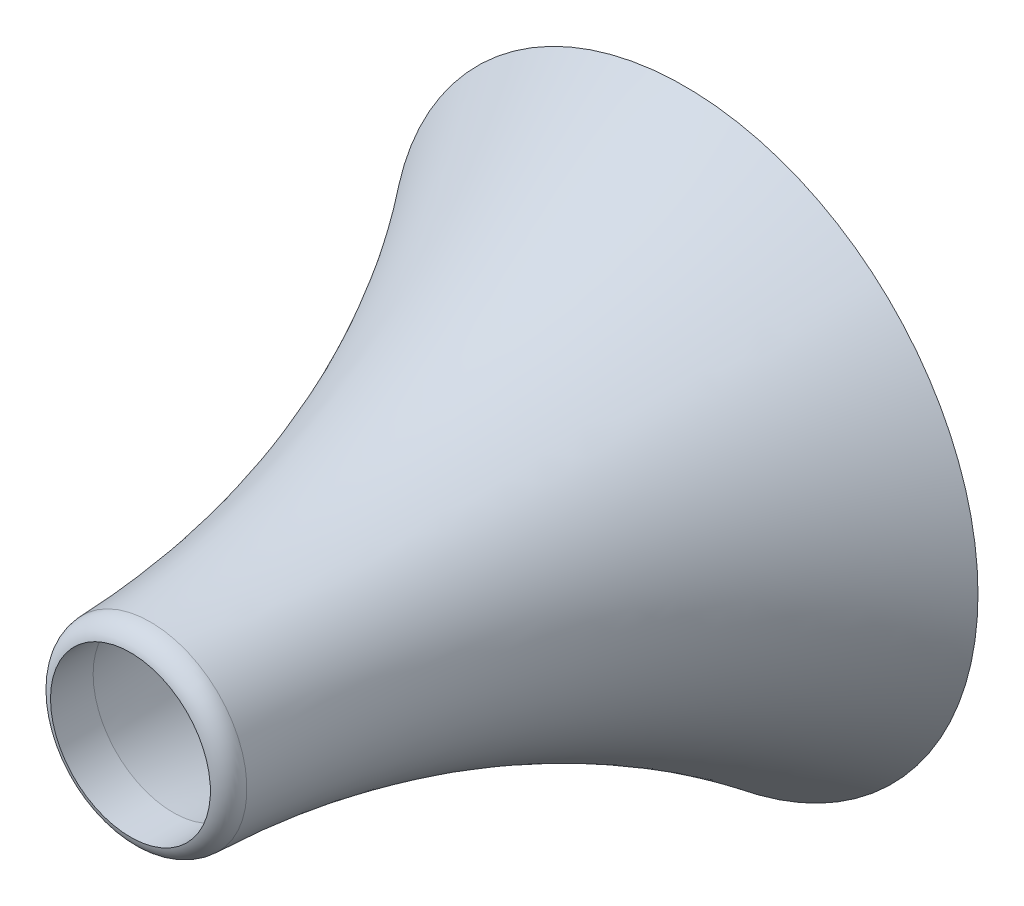
SolidWorks part; units mm, degrees
ref_plane "Front Plane" through (0, 0, 0) normal (0, 0, 1) x (1, 0, 0)
ref_plane "Top Plane" through (0, 0, 0) normal (0, 1, 0) x (1, 0, 0)
ref_plane "Right Plane" through (0, 0, 0) normal (1, 0, 0) x (0, 0, -1)
sketch "Sketch1" plane through (0, 0, 0) normal (0, 1, 0) x (1, 0, 0)
  line L0 (-40, 0) -> (-55, 0)
  line L1 (-40, -4) -> (-48, -4)
  line L2 (-15, -104) -> (-18, -104)
  line L4 (0, 34.5868) -> (0, -96) construction
  line L5 (0, -96) -> (0, -124.9152) construction
  line L6 (-40, 0) -> (-40, -4)
  line L8 (-15, -96) -> (-15, -104)
  spline S0 degree 2 poles (-55, 0) (-18.7451, -47.008) (-18, -104) knots 0 0 0 1 1 1
  spline S1 degree 2 poles (-48, -4) (-20.1246, -45.4419) (-15, -96) knots 0 0 0 1 1 1
  dimension "D8" = 40
  dimension "D2" = 18
  dimension "D1" = 8
  dimension "D3" = 4
  dimension "D4" = 40
  dimension "D5" = 15
  dimension "D6" = 55
  dimension "D7" = 104
revolve "Revolve2" add sketch "Sketch1" angle 360 about L4
fillet "Fillet5" radius 4 1 edges at (-18, 0, 104)
